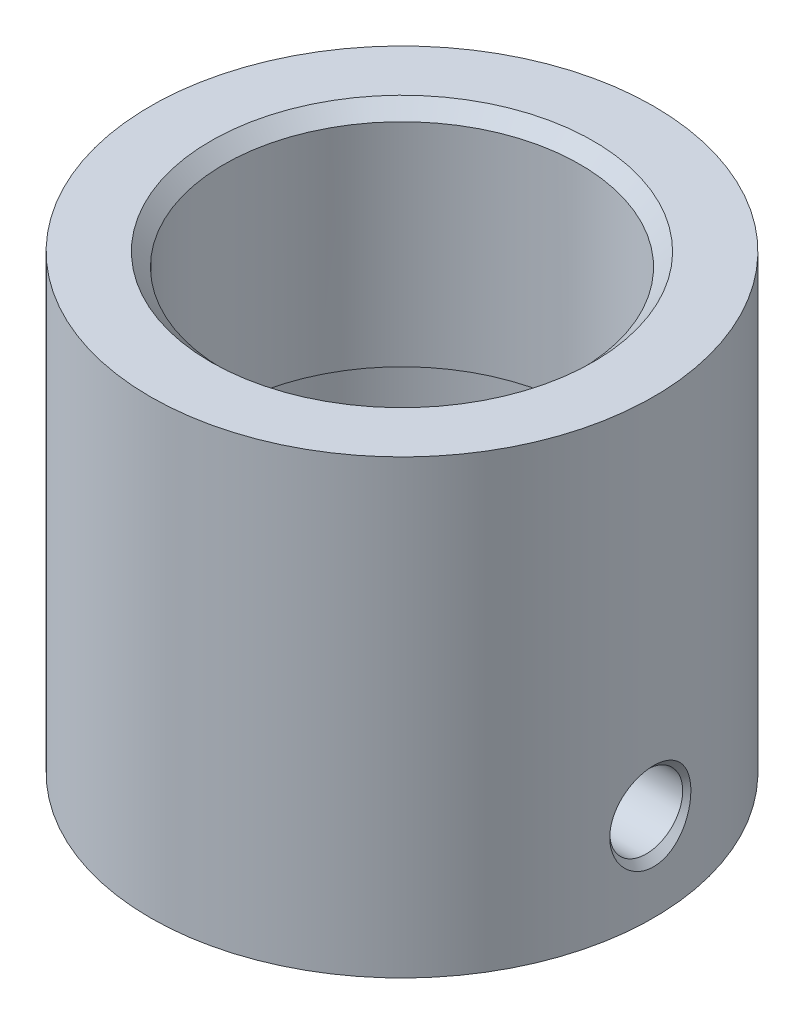
SolidWorks part; units mm, degrees
material "AISI 1020"
ref_plane "Plano superior" through (0, 0, 0) normal (0, 0, 1) x (1, 0, 0)
ref_plane "Plano frontal" through (0, 0, 0) normal (0, 1, 0) x (1, 0, 0)
ref_plane "Plano direito" through (0, 0, 0) normal (1, 0, 0) x (0, 0, -1)
sketch "Esboço1" plane through (0, 0, 0) normal (0, 1, 0) x (1, 0, 0)
  circle A0 centre (0, 0) radius 14.5
  dimension "D1" = 29
extrude "Ressalto-extrusão1" add sketch "Esboço1" along normal blind 26
sketch "Esboço2" plane through (0, 0, 0) normal (0, -1, 0) x (1, 0, 0)
  circle A0 centre (0, 0) radius 10.5
  dimension "D1" = 21
extrude "Corte-extrusão2" cut sketch "Esboço2" against normal blind 13 contours A0
hole_wizard "Furo roscado de M22x1.51" positions "Esboço4" profile "Esboço5" tap size "M22x1.5" standard "DIN" end condition up to next
sketch "Esboço4" plane through (0, 26, 0) normal (0, 1, 0) x (1, 0, 0)
  point P0 (0, 0)
sketch "Esboço5" plane through (0, 26, 0) normal (1, 0, 0) x (0, 0, 1)
  line L0 (0, 0) -> (0, 13)
  line L1 (0, 13) -> (10.25, 13)
  line L2 (10.25, 13) -> (10.25, 0.775)
  line L3 (10.25, 0.775) -> (11.025, 0)
  line L5 (11.025, 0) -> (0, 0)
  line L6 (-10.25, 0.775) -> (-11.025, 0) construction
  line L11 (0, -6.35) -> (0, 107.95) construction
  dimension "Thru Tap Drill Dia." = 20.5
  dimension "Thru Tap Drill Depth" = 13
  dimension "Near C'Sink Dia." = 22.05
  dimension "Near C'Sink Angle" = 90
cosmetic thread "Rosca de furo1" parameters "D2"=22
hole_wizard "Furo roscado de M51" positions "3DSketch3" profile "Esboço13" tap size "M5" standard "DIN" end condition up to next
sketch3d "3DSketch3"
  circle A0 centre (0, 0, 0) radius 14.5 construction
  point P0 (14.5, 5.0759, 0.0042)
  point P5 (0, 14.5, 0)
  dimension "D1" = 15.3628
sketch "Esboço13" plane through (14.5, 5.0759, 0.0042) normal (0, 1, 0) x (0.0003, 0, -1)
  line L0 (0, 0) -> (0, 4)
  line L1 (0, 4) -> (2.1, 4)
  line L2 (2.1, 4) -> (2.1, 0.425)
  line L3 (2.1, 0.425) -> (2.525, 0)
  line L5 (2.525, 0) -> (0, 0)
  line L6 (-2.1, 0.425) -> (-2.525, 0) construction
  line L11 (0, -6.35) -> (0, 107.95) construction
  dimension "Thru Tap Drill Dia." = 4.2
  dimension "Thru Tap Drill Depth" = 4
  dimension "Near C'Sink Dia." = 5.05
  dimension "Near C'Sink Angle" = 90
cosmetic thread "Rosca de furo2"
